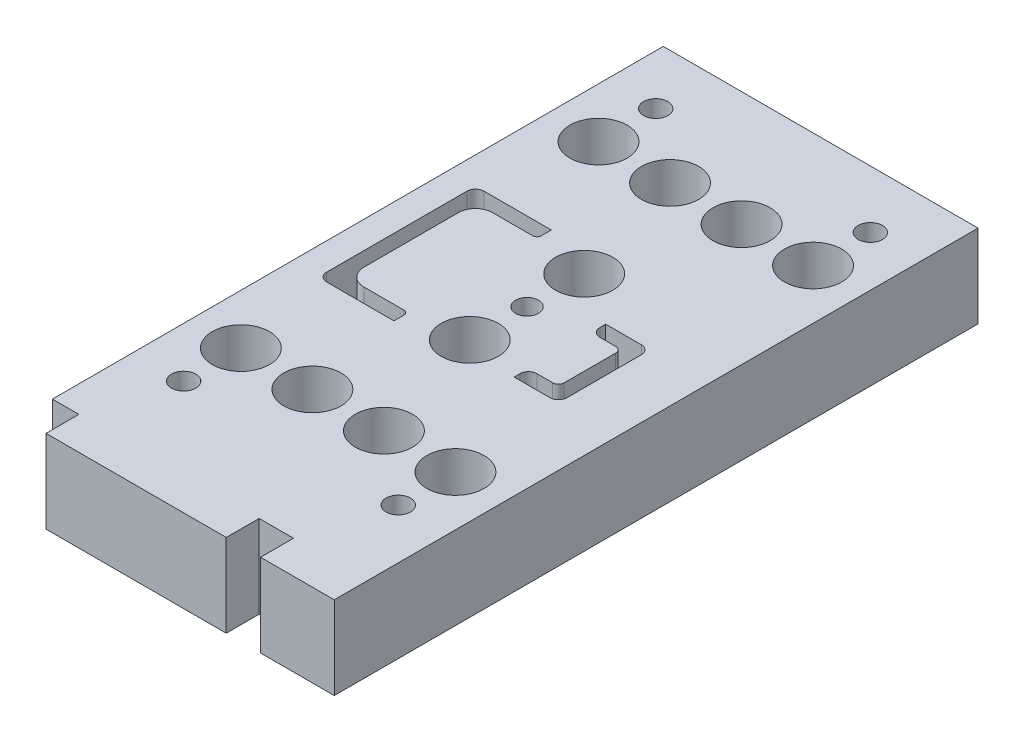
SolidWorks part; units mm, degrees
material "Plain Carbon Steel"
ref_plane "Front Plane" through (0, 0, 0) normal (0, 0, 1) x (1, 0, 0)
ref_plane "Top Plane" through (0, 0, 0) normal (0, 1, 0) x (1, 0, 0)
ref_plane "Right Plane" through (0, 0, 0) normal (1, 0, 0) x (0, 0, -1)
sketch "Sketch1" plane through (0, 0, 0) normal (0, 1, 0) x (1, 0, 0)
  line L1 (-55, -112.5) -> (55, -112.5)
  line L2 (-55, -112.5) -> (-55, 112.5)
  line L3 (-55, 112.5) -> (55, 112.5)
  line L4 (55, -112.5) -> (55, 112.5)
  line L5 (-55, -112.5) -> (55, 112.5) construction
  line L6 (-55, 112.5) -> (55, -112.5) construction
  point P0 (0, 0)
  dimension "D1" = 110
  dimension "D2" = 225
extrude "Boss-Extrude1" add sketch "Sketch1" against normal blind 29
sketch "Sketch2" plane through (0, 0, 0) normal (0, 1, 0) x (1, 0, 0)
  line L0 (-19, 37.36) -> (-19, 33.86) construction
  line L1 (-42.5, 37.36) -> (-19, 37.36) construction
  line L2 (-45.5, 34.36) -> (-45.5, -14.64) construction
  line L3 (-42.5, -17.64) -> (-19, -17.64) construction
  line L4 (-19, -17.64) -> (-19, -14.14) construction
  line L5 (-34.5, -12.64) -> (-20.5, -12.64) construction
  line L6 (-40.5, 26.36) -> (-40.5, -6.64) construction
  line L7 (-20.5, 32.36) -> (-34.5, 32.36) construction
  line L8 (-19, 37.36) -> (-19, 33.86)
  line L9 (-42.5, 37.36) -> (-19, 37.36)
  line L10 (-45.5, 34.36) -> (-45.5, -14.64)
  line L11 (-42.5, -17.64) -> (-19, -17.64)
  line L12 (-19, -17.64) -> (-19, -14.14)
  line L13 (-34.5, -12.64) -> (-20.5, -12.64)
  line L14 (-40.5, 26.36) -> (-40.5, -6.64)
  line L15 (-20.5, 32.36) -> (-34.5, 32.36)
  arc A0 (-20.5, 32.36) -> (-19, 33.86) centre (-20.5, 33.86) ccw construction
  arc A1 (-42.5, 37.36) -> (-45.5, 34.36) centre (-42.5, 34.36) ccw construction
  arc A2 (-45.5, -14.64) -> (-42.5, -17.64) centre (-42.5, -14.64) ccw construction
  arc A3 (-19, -14.14) -> (-20.5, -12.64) centre (-20.5, -14.14) ccw construction
  arc A4 (-40.5, -6.64) -> (-34.5, -12.64) centre (-34.5, -6.64) ccw construction
  arc A5 (-34.5, 32.36) -> (-40.5, 26.36) centre (-34.5, 26.36) ccw construction
  arc A6 (-20.5, 32.36) -> (-19, 33.86) centre (-20.5, 33.86) ccw
  arc A7 (-42.5, 37.36) -> (-45.5, 34.36) centre (-42.5, 34.36) ccw
  arc A8 (-45.5, -14.64) -> (-42.5, -17.64) centre (-42.5, -14.64) ccw
  arc A9 (-19, -14.14) -> (-20.5, -12.64) centre (-20.5, -14.14) ccw
  arc A10 (-40.5, -6.64) -> (-34.5, -12.64) centre (-34.5, -6.64) ccw
  arc A11 (-34.5, 32.36) -> (-40.5, 26.36) centre (-34.5, 26.36) ccw
extrude "Cut-Extrude1" cut sketch "Sketch2" against normal up to next
sketch "Sketch3" plane through (0, 0, 0) normal (0, 1, 0) x (1, 0, 0)
  line L0 (19, 18.36) -> (31.5, 18.36) construction
  line L1 (19, 18.36) -> (19, 16.36) construction
  line L2 (27.5, 13.36) -> (22, 13.36) construction
  line L3 (29.5, -6.64) -> (29.5, 11.36) construction
  line L4 (22, -8.64) -> (27.5, -8.64) construction
  line L5 (19, -13.64) -> (19, -11.64) construction
  line L6 (31.5, -13.64) -> (19, -13.64) construction
  line L7 (34.5, 15.36) -> (34.5, -10.64) construction
  line L8 (19, 18.36) -> (31.5, 18.36)
  line L9 (19, 18.36) -> (19, 16.36)
  line L10 (27.5, 13.36) -> (22, 13.36)
  line L11 (29.5, -6.64) -> (29.5, 11.36)
  line L12 (22, -8.64) -> (27.5, -8.64)
  line L13 (19, -13.64) -> (19, -11.64)
  line L14 (31.5, -13.64) -> (19, -13.64)
  line L15 (34.5, 15.36) -> (34.5, -10.64)
  arc A0 (34.5, 15.36) -> (31.5, 18.36) centre (31.5, 15.36) ccw construction
  arc A1 (19, 16.36) -> (22, 13.36) centre (22, 16.36) ccw construction
  arc A2 (29.5, 11.36) -> (27.5, 13.36) centre (27.5, 11.36) ccw construction
  arc A3 (27.5, -8.64) -> (29.5, -6.64) centre (27.5, -6.64) ccw construction
  arc A4 (22, -8.64) -> (19, -11.64) centre (22, -11.64) ccw construction
  arc A5 (31.5, -13.64) -> (34.5, -10.64) centre (31.5, -10.64) ccw construction
  arc A6 (34.5, 15.36) -> (31.5, 18.36) centre (31.5, 15.36) ccw
  arc A7 (19, 16.36) -> (22, 13.36) centre (22, 16.36) ccw
  arc A8 (29.5, 11.36) -> (27.5, 13.36) centre (27.5, 11.36) ccw
  arc A9 (27.5, -8.64) -> (29.5, -6.64) centre (27.5, -6.64) ccw
  arc A10 (22, -8.64) -> (19, -11.64) centre (22, -11.64) ccw
  arc A11 (31.5, -13.64) -> (34.5, -10.64) centre (31.5, -10.64) ccw
extrude "Cut-Extrude2" cut sketch "Sketch3" against normal up to next
sketch "Sketch4" plane through (0, -29, 0) normal (0, -1, 0) x (1, 0, 0)
  circle A0 centre (0, 100) radius 8.5
  circle A1 centre (0, -100) radius 8.5
  dimension "D1" = 17
extrude "Cut-Extrude3" cut sketch "Sketch4" against normal blind 5
sketch "Sketch5" plane through (0, 0, 0) normal (0, 1, 0) x (1, 0, 0)
  line L2 (-55, 112.5) -> (-55, -112.5) construction
  line L5 (-19, 37.36) -> (-42.5, 37.36) construction
  line L6 (-40.5, 9.86) -> (29.5, 9.86) construction
  line L7 (-40.5, -6.64) -> (-40.5, 26.36) construction
  line L9 (29.5, 11.36) -> (29.5, -6.64) construction
  circle A0 centre (-37.5, 72.36) radius 10
  circle A1 centre (-12.5, 72.36) radius 10
  circle A2 centre (12.5, 72.36) radius 10
  circle A3 centre (37.5, 72.36) radius 10
  circle A4 centre (37.5, -52.64) radius 10
  circle A5 centre (12.5, -52.64) radius 10
  circle A6 centre (-12.5, -52.64) radius 10
  circle A7 centre (-37.5, -52.64) radius 10
  circle A8 centre (0, 29.86) radius 10
  circle A9 centre (0, -10.14) radius 10
  dimension "D1" = 20
  dimension "D2" = 17.5
  dimension "D3" = 35
  dimension "D5" = 25
  dimension "D6" = 20
  dimension "D7" = 20
  dimension "D4" = 4
extrude "Cut-Extrude4" cut sketch "Sketch5" against normal blind 20
sketch "Sketch6" plane through (0, 0, 0) normal (0, 1, 0) x (1, 0, 0)
  line L0 (-55, -112.5) -> (55, -112.5) construction
  line L1 (29.25, -112.5) -> (17.25, -112.5)
  line L2 (29.25, -112.5) -> (29.25, -101)
  line L3 (29.25, -101) -> (17.25, -101)
  line L4 (17.25, -112.5) -> (17.25, -101)
  line L5 (18.75, -102) -> (27.75, -102) construction
  line L6 (-45.75, -112.5) -> (-57.75, -112.5)
  line L7 (-45.75, -112.5) -> (-45.75, -101)
  line L8 (-45.75, -101) -> (-57.75, -101)
  line L9 (-57.75, -112.5) -> (-57.75, -101)
  line L10 (28.25, -102.5) -> (28.25, -115) construction
  line L11 (18.25, -115) -> (18.25, -102.5) construction
  line L12 (-56.75, -115) -> (-56.75, -102.5) construction
  line L13 (-46.75, -102.5) -> (-46.75, -115) construction
  line L14 (-56.25, -102) -> (-47.25, -102) construction
  dimension "D1" = 1
  dimension "D2" = 1
  dimension "D3" = 1
  dimension "D4" = 1
  dimension "D5" = 1
  dimension "D6" = 1
extrude "Cut-Extrude5" cut sketch "Sketch6" against normal up to next
hole_wizard "M10 Tapped Hole1" positions "Sketch9" profile "Sketch8" tap size "M10" standard "ISO" end condition through all
sketch "Sketch9" plane through (0, 0, 0) normal (0, 1, 0) x (1, 0, 0)
  line L2 (-37.5, 72.36) -> (-37.5, 92.36) construction
  line L4 (37.5, 72.36) -> (37.5, 92.36) construction
  circle A1 centre (-37.5, 72.36) radius 10 construction
  circle A2 centre (-37.5, -52.64) radius 10 construction
  point P0 (-37.5, -72.64)
  point P2 (37.5, -72.64)
  point P4 (37.5, 92.36)
  point P6 (-37.5, 92.36)
  dimension "D1" = 20
  dimension "D2" = 20
sketch "Sketch8" plane through (-37.5, 0, 72.64) normal (1, 0, 0) x (0, 0, 1)
  line L0 (0, 0) -> (0, 29)
  line L1 (0, 29) -> (4.25, 29)
  line L2 (4.25, 29) -> (4.25, 0)
  line L5 (4.25, 0) -> (0, 0)
  line L11 (0, -6.35) -> (0, 107.95) construction
  dimension "Thru Tap Drill Dia." = 8.5
  dimension "Thru Tap Drill Depth" = 29
cosmetic thread "Hole Thread1" parameters "D2"=10
cosmetic thread "Hole Thread2" parameters "D2"=10
cosmetic thread "Hole Thread3" parameters "D2"=10
cosmetic thread "Hole Thread4" parameters "D2"=10
sketch "Sketch10" plane through (0, 0, 0) normal (0, 1, 0) x (1, 0, 0)
  circle A0 centre (0, 9.86) radius 5 construction
  circle A1 centre (0, 9.86) radius 5 construction
  circle A2 centre (0, 9.86) radius 4
  dimension "D1" = 8
extrude "Cut-Extrude6" cut sketch "Sketch10" against normal up to next
